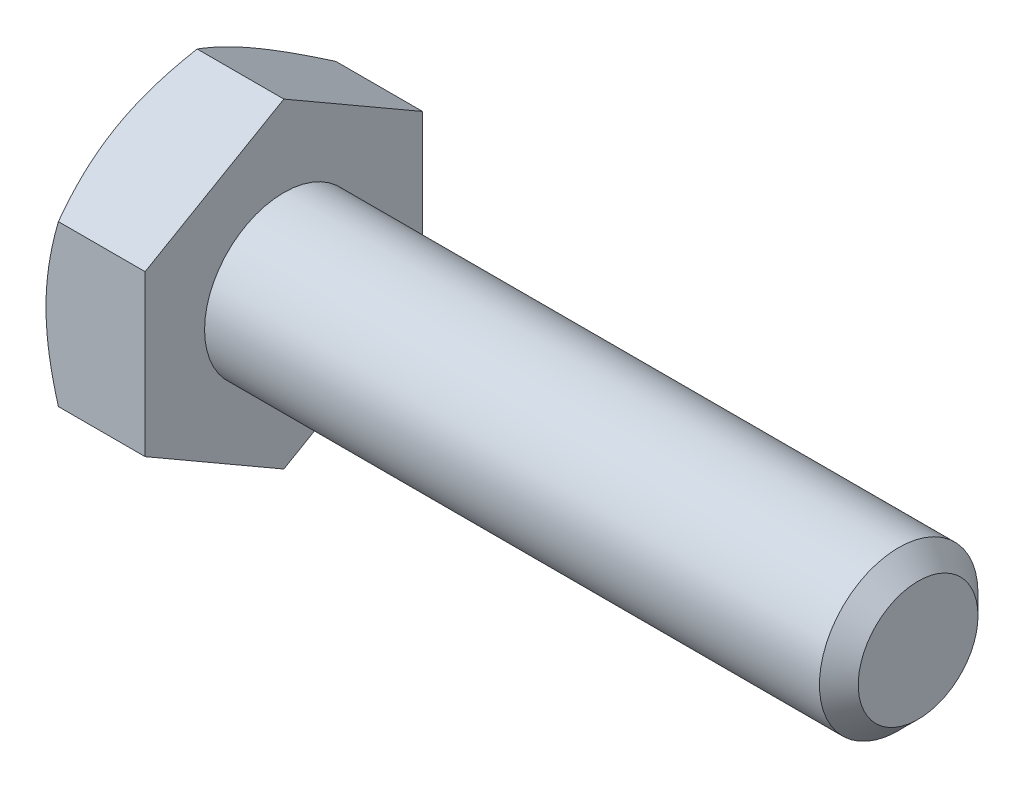
SolidWorks part; units mm, degrees
material "Alloy Steel"
ref_plane "Front Plane" through (0, 0, 0) normal (0, 0, 1) x (1, 0, 0)
ref_plane "Top Plane" through (0, 0, 0) normal (0, 1, 0) x (1, 0, 0)
ref_plane "Right Plane" through (0, 0, 0) normal (1, 0, 0) x (0, 0, -1)
sketch "Sketch1" plane through (0, 0, 0) normal (0, 0, 1) x (1, 0, 0)
  line L0 (-14.6844, 0) -> (14.6844, 0) construction
  line L1 (14.6844, 3.175) -> (14.6844, -3.175) construction
  line L2 (-10.7156, 5.5562) -> (-10.7156, -5.5562) construction
  line L3 (-14.6844, 5.5562) -> (-14.6844, -5.5562) construction
  point P9 (-10.7156, 0)
  point P10 (10.2394, -3.175)
  dimension "D1" = 4.445
  dimension "Screw Dia" = 6.35
  dimension "Hex" = 11.1125
  dimension "Head Ht" = 3.9688
  dimension "Screw Lenght" = 25.4
ref_plane "Plane2" through (14.6844, 0, 0) normal (1, 0, 0) x (0, 0, -1)
sketch "Sketch5" plane through (14.6844, 0, 0) normal (1, 0, 0) x (0, 0, -1)
  circle A0 centre (0, 0) radius 3.175
extrude "Boss-Extrude3" add sketch "Sketch5" against normal up to vertex (25.4 mm away) up to point (-10.7156, 0, 0)
sketch "Sketch9" plane through (14.6844, 0, 0) normal (1, 0, 0) x (0, 0, -1)
  circle A1 centre (0, 0) radius 3.175
  circle A2 centre (0, 0) radius 3.175
  dimension "D1" = 0
curve "Helix/Spiral1" pitch 1.27 height 26.67 turns 21 parameters "Pitch"=1.27
chamfer "Chamfer1" distance 0.7772 angle 45 1 edges at (14.6844, 0, -3.175)
sketch "Sketch10" plane through (0, 0, 0) normal (0, 0, 1) x (1, 0, 0)
  line L0 (14.6844, 3.175) -> (15.1606, 2.3501)
  line L1 (15.1606, 2.3501) -> (15.3194, 2.3501)
  line L2 (15.3194, 2.3501) -> (15.7956, 3.175)
  line L3 (14.6844, 3.175) -> (15.7956, 3.175)
  line L4 (15.24, 3.175) -> (15.24, 2.3501) construction
  line L5 (14.9225, 2.7626) -> (15.5575, 2.7626) construction
  dimension "D1" = 60
  dimension "D2" = 0.1588
  dimension "D3" = 0.635
sketch "Sketch6" plane through (-10.7156, 0, 0) normal (-1, 0, 0) x (0, 0, 1)
  line L0 (0, 5.5562) -> (0, -5.5562) construction
  line L1 (5.5563, 3.2079) -> (0, 6.4158)
  line L2 (0, 6.4158) -> (-5.5562, 3.2079)
  line L3 (-5.5562, 3.2079) -> (-5.5562, -3.2079)
  line L4 (-5.5562, -3.2079) -> (0, -6.4158)
  line L5 (0, -6.4158) -> (5.5563, -3.2079)
  line L6 (5.5563, -3.2079) -> (5.5563, 3.2079)
  circle A0 centre (0, 0) radius 5.5563 construction
extrude "Boss-Extrude4" add sketch "Sketch6" along normal up to vertex (3.9688 mm away) up to point (-14.6844, -5.5562, 0)
sketch "Sketch7" plane through (-14.6844, 0, 0) normal (-1, 0, 0) x (0, 0, 1)
  circle A0 centre (0, 0) radius 5.5563 construction
  circle A1 centre (0, 0) radius 5.5563
sketch "Sketch8" plane through (-14.6844, 0, 0) normal (-1, 0, 0) x (0, 0, 1)
  circle A0 centre (0, 0) radius 5.5563 construction
  circle A1 centre (0, 0) radius 5.5563
extrude "Cut-Extrude3" cut sketch "Sketch8" against normal through all draft 60 flip side to cut
sketch "Sketch12" plane through (-14.6844, 0, 0) normal (-1, 0, 0) x (0, 0, 1)
  line L0 (0, 4.2783) -> (0, 2.3892) construction
  line L1 (0.1667, 4.2783) -> (0.1667, 2.3892)
  line L2 (-0.1667, 4.2783) -> (-0.1667, 2.3892)
  line L3 (0, 3.175) -> (0, -3.175) construction
  arc A0 (0.1667, 4.2783) -> (-0.1667, 4.2783) centre (0, 4.2783) ccw
  arc A1 (-0.1667, 2.3892) -> (0.1667, 2.3892) centre (0, 2.3892) ccw
  circle A3 centre (0, 0) radius 2.2225 construction
  circle A4 centre (0, 0) radius 4.445 construction
  point P2 (0, 3.3337)
  dimension "D1" = 4.445
  dimension "D3" = 8.89
  dimension "D2" = 0.3334
extrude "Cut-Extrude4" cut sketch "Sketch12" against normal blind 0.254
pattern_circular "CirPattern1" count 3 over 360 about axis through (-10.7156, 0, 0) along (1, 0, 0) of "Cut-Extrude4"
equation "\"D2@Sketch10\" = \"Pitch@Helix/Spiral1\"*.125"
equation "\"D3@Sketch10\" = \"Pitch@Helix/Spiral1\"*.5"
equation "\"D1@Chamfer1\" = \"Pitch@Helix/Spiral1\"*.612"
equation "\"D1@Sketch12\" = \"Hex@Sketch1\"*.4"
equation "\"D3@Sketch12\" = \"Hex@Sketch1\"*.8"
equation "\"D2@Sketch12\" = \"Hex@Sketch1\"*.03"
equation "\"D1@Sketch1\" = \"Pitch@Helix/Spiral1\"*3.5"
equation "\"D3@Helix/Spiral1\" = \"Screw Lenght@Sketch1\"+\"Pitch@Helix/Spiral1\""
